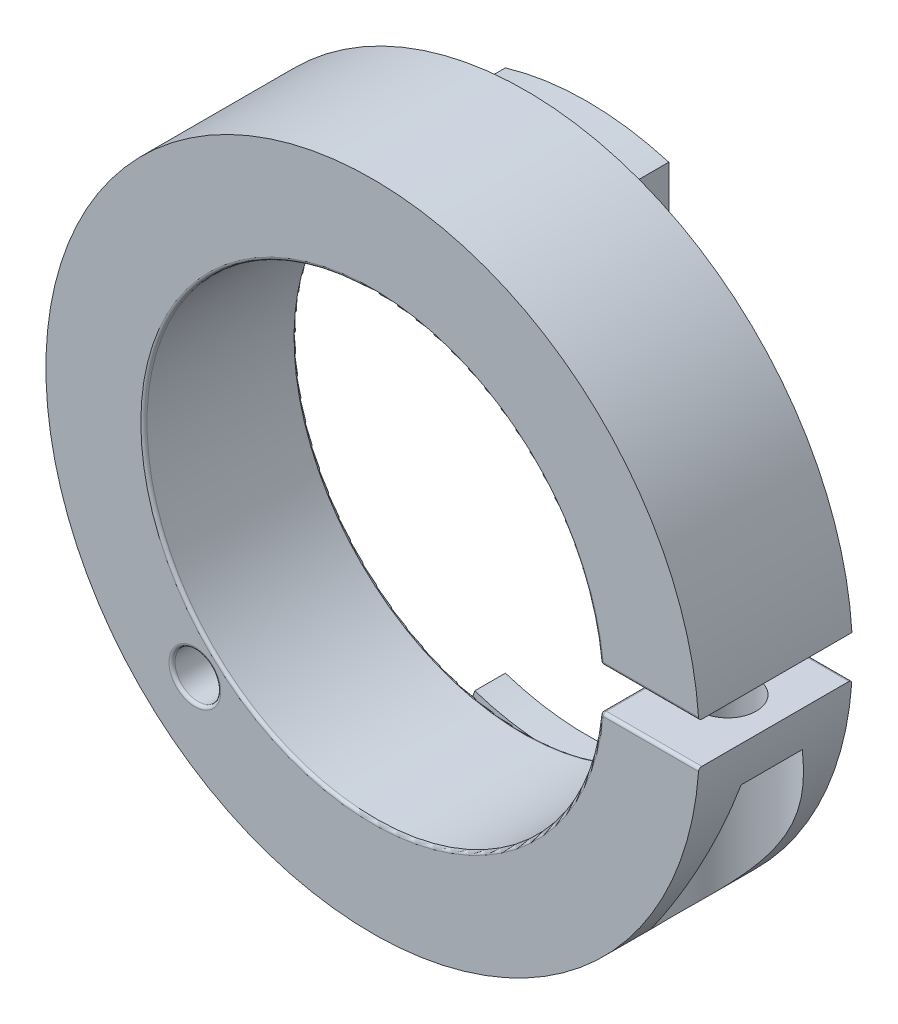
SolidWorks part; units mm, degrees
material "ABS"
ref_plane "Front Plane" through (0, 0, 0) normal (0, 0, 1) x (1, 0, 0)
ref_plane "Top Plane" through (0, 0, 0) normal (0, 1, 0) x (1, 0, 0)
ref_plane "Right Plane" through (0, 0, 0) normal (1, 0, 0) x (0, 0, -1)
sketch "Sketch2" plane through (0, 0, 0) normal (0, 0, 1) x (1, 0, 0)
  circle A0 centre (-85.2244, 56.7775) radius 16.2304 construction
  circle A3 centre (-85.2244, 56.7775) radius 16
  dimension "D1" = 32
extrude "Boss-Extrude1" add sketch "Sketch2" along normal blind 7.5
sketch "Sketch3" plane through (0, 0, 7.5) normal (0, 0, 1) x (1, 0, 0)
  circle A0 centre (-85.2244, 56.7775) radius 11.2
  circle A1 centre (-85.2244, 56.7775) radius 16 construction
  dimension "D1" = 22.4
extrude "Cut-Extrude1" cut sketch "Sketch3" against normal through all
sketch "Sketch4" plane through (0, 0, 7.5) normal (0, 0, 1) x (1, 0, 0)
  line L0 (-85.2244, 56.7775) -> (-60.628, 56.7775) construction
  line L2 (-75.2244, 57.7775) -> (-63.2244, 57.7775)
  line L3 (-75.2244, 57.7775) -> (-75.2244, 55.7775)
  line L4 (-75.2244, 55.7775) -> (-63.2244, 55.7775)
  line L5 (-63.2244, 57.7775) -> (-63.2244, 55.7775)
  line L6 (-75.2244, 57.7775) -> (-63.2244, 55.7775) construction
  line L7 (-75.2244, 55.7775) -> (-63.2244, 57.7775) construction
  circle A0 centre (-85.2244, 56.7775) radius 13.05 construction
  circle A2 centre (-85.2244, 56.7775) radius 16 construction
  point P2 (-69.2244, 56.7775)
  dimension "D1" = 12
  dimension "D2" = 2
  dimension "D3" = 10
extrude "Cut-Extrude2" cut sketch "Sketch4" against normal through all
fillet "Fillet2" radius 0.15 2 edges at (-71.6624, 57.7775, 7.5) (-74.0692, 55.7775, 3.75)
ref_axis "Axis1" through (-74.0692, 57.7775, 7.35) along (0.5479, 0, -0.8366)
ref_axis "Axis2" through (-69.2557, 57.7775, 7.35) along (-0.5479, 0, -0.8366)
ref_point "Point1"
sketch "Sketch5" plane through (0, 55.7775, 0) normal (0, 1, 0) x (1, 0, 0)
  circle A0 centre (-71.6624, -3.675) radius 2.625
  dimension "D1" = 5.25
extrude "Cut-Extrude3" cut sketch "Sketch5" against normal through all from offset 2 offset against normal yes
sketch "Sketch6" plane through (0, 55.7775, 0) normal (0, 1, 0) x (1, 0, 0)
  circle A0 centre (-71.6624, -3.675) radius 1.3978
extrude "Cut-Extrude4" cut sketch "Sketch6" against normal through all
sketch "Sketch19" plane through (0, 0, 0) normal (0, 0, -1) x (-1, 0, 0)
  line L2 (81.2244, 67.2388) -> (81.2244, 70.2388)
  line L3 (89.2244, 67.2388) -> (89.2244, 70.2388)
  line L4 (73.9328, 55.7775) -> (69.2557, 55.7775)
  line L5 (69.2557, 57.7775) -> (74.0692, 57.7775)
  arc A0 (81.2244, 70.2388) -> (89.2244, 70.2388) centre (85.2244, 56.7775) cw
  arc A1 (74.0821, 55.6427) -> (74.0692, 57.7775) centre (85.2244, 56.7775) ccw construction
  arc A5 (74.0821, 55.6427) -> (74.0692, 57.7775) centre (85.2244, 56.7775) ccw
  arc A6 (74.0821, 55.6427) -> (73.9328, 55.7775) centre (73.9328, 55.6275) ccw
  arc A7 (69.2557, 55.7775) -> (69.2557, 57.7775) centre (85.2244, 56.7775) ccw
  arc A8 (89.2244, 67.2388) -> (81.2244, 67.2388) centre (85.2244, 56.7775) ccw
  point P4 (85.2244, 67.9775)
  dimension "D1" = 3
  dimension "D2" = 4
  dimension "D3" = 4
  dimension "D4" = 0
extrude "Boss-Extrude2" add sketch "Sketch19" along normal blind 3
sketch "Sketch23" plane through (0, 0, 0) normal (0, 0, -1) x (-1, 0, 0)
  line L0 (80.2412, 41.5733) -> (81.2244, 44.5733)
  line L1 (90.2077, 41.5733) -> (89.2244, 44.5733)
  arc A0 (80.2412, 41.5733) -> (90.2077, 41.5733) centre (85.2244, 56.7775) ccw
  arc A1 (69.2557, 55.7775) -> (69.2557, 57.7775) centre (85.2244, 56.7775) ccw construction
  arc A2 (81.2244, 44.5733) -> (89.2244, 44.5733) centre (85.2244, 56.7775) ccw
  arc A3 (74.0821, 55.6427) -> (89.2244, 67.2388) centre (85.2244, 56.7775) ccw construction
  point P9 (85.2244, 45.5775)
  dimension "D1" = 4
  dimension "D2" = 4
  dimension "D3" = 3
extrude "Boss-Extrude3" add sketch "Sketch23" along normal blind 3
sketch "Sketch25" plane through (0, 0, 0) normal (0, 0, -1) x (-1, 0, 0)
  line L0 (89.2244, 67.2388) -> (89.2244, 70.2388) construction
  line L2 (90.2077, 41.5733) -> (89.2244, 44.5733) construction
  line L3 (81.2244, 70.2388) -> (81.2244, 69.2388)
  line L4 (81.2244, 70.2388) -> (81.2244, 67.2388) construction
  line L6 (81.2244, 44.5733) -> (80.8967, 43.5733)
  line L7 (81.2244, 44.5733) -> (80.2412, 41.5733) construction
  line L8 (89.2244, 44.5733) -> (89.5522, 43.5733)
  line L9 (90.2077, 41.5733) -> (89.2244, 44.5733) construction
  line L10 (89.2244, 70.2388) -> (89.2244, 69.2388)
  line L11 (89.2244, 67.2388) -> (89.2244, 70.2388) construction
  arc A0 (81.2244, 70.2388) -> (89.2244, 70.2388) centre (85.2244, 56.7775) cw
  arc A2 (81.2244, 44.5733) -> (89.2244, 44.5733) centre (85.2244, 56.7775) ccw
  arc A3 (89.2244, 70.2388) -> (81.2244, 70.2388) centre (85.2244, 56.7775) ccw construction
  arc A4 (80.8967, 43.5733) -> (89.5522, 43.5733) centre (85.2244, 56.7775) ccw
  arc A5 (81.2244, 69.2388) -> (89.2244, 69.2388) centre (85.2244, 56.7775) cw
  dimension "D1" = 1
  dimension "D2" = 1
extrude "Cut-Extrude12" cut sketch "Sketch25" along normal blind 1.5
sketch "Sketch26" plane through (0, 0, 0) normal (0, 0, -1) x (-1, 0, 0)
  line L0 (85.2244, 56.7775) -> (95.5888, 44.5882) construction
  line L1 (93.2244, 47.3688) -> (93.9863, 48.0166) construction
  line L2 (92.9005, 47.7498) -> (93.6624, 48.3975) construction
  line L3 (93.5483, 46.9879) -> (94.3101, 47.6357) construction
  line L4 (93.8722, 46.607) -> (94.634, 47.2548) construction
  line L5 (93.5483, 46.9879) -> (94.3101, 47.6357) construction
  line L6 (94.1961, 46.2261) -> (94.9579, 46.8739) construction
  arc A0 (93.5483, 46.9879) -> (94.1961, 46.2261) centre (93.8722, 46.607) ccw construction
  arc A1 (94.9579, 46.8739) -> (94.3101, 47.6357) centre (94.634, 47.2548) ccw construction
  arc A2 (90.2077, 41.5733) -> (69.2557, 57.7775) centre (85.2244, 56.7775) ccw construction
  arc A3 (74.0821, 55.6427) -> (89.2244, 67.2388) centre (85.2244, 56.7775) ccw construction
  arc A4 (92.9005, 47.7498) -> (93.5483, 46.9879) centre (93.2244, 47.3688) ccw construction
  arc A5 (94.3101, 47.6357) -> (93.6624, 48.3975) centre (93.9863, 48.0166) ccw construction
  circle A6 centre (93.9292, 47.3118) radius 1.118
  point P2 (94.2531, 46.9309)
  point P6 (92.4795, 48.245)
  point P7 (93.2244, 47.3688)
  point P11 (93.6053, 47.6927)
  dimension "D1" = 1.15
  dimension "D2" = 8
  dimension "D3" = 1
  dimension "D4" = 1
  dimension "D5" = 1
  dimension "D6" = 1
  dimension "D7" = 1
extrude "Cut-Extrude13" cut sketch "Sketch26" against normal through all
fillet "Fillet4" radius 0.15 14 edges at (-71.5943, 55.7775, 0) (-74.0334, 55.7388, 0) (-71.5943, 55.7775, 7.5) (-74.0334, 55.7388, 7.5) (-76.2913, 63.5332, 0) (-92.0341, 47.8854, 0) (-96.4244, 56.7698, 7.5) (-74.0721, 57.8101, 7.4434) (-74.0692, 57.7775, 3.675) (-85.2244, 67.9775, -3) (-81.2244, 67.2388, -1.5) (-89.2244, 67.2388, -1.5) (-95.0473, 47.3118, 0) (-95.0473, 47.3118, 7.5)
sketch "Sketch20" plane through (0, 57.7775, 0) normal (0, -1, 0) x (1, 0, 0)
  circle A0 centre (-71.6624, 3.675) radius 0.6
extrude "Cut-Extrude11" cut sketch "Sketch20" against normal blind 3
